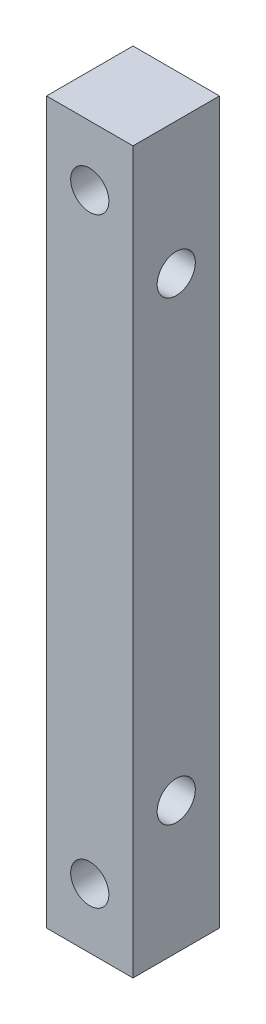
SolidWorks part; units mm, degrees
material "6061-T6 (SS)"
ref_plane "Front Plane" through (0, 0, 0) normal (0, 0, 1) x (1, 0, 0)
ref_plane "Top Plane" through (0, 0, 0) normal (0, 1, 0) x (1, 0, 0)
ref_plane "Right Plane" through (0, 0, 0) normal (1, 0, 0) x (0, 0, -1)
sketch "Sketch1" plane through (0, 0, 0) normal (0, 1, 0) x (1, 0, 0)
  line L1 (-4.572, 4.572) -> (4.572, 4.572)
  line L2 (-4.572, 4.572) -> (-4.572, -4.572)
  line L3 (-4.572, -4.572) -> (4.572, -4.572)
  line L4 (4.572, 4.572) -> (4.572, -4.572)
  line L5 (-4.572, 4.572) -> (4.572, -4.572) construction
  line L6 (-4.572, -4.572) -> (4.572, 4.572) construction
  point P0 (0, 0)
  dimension "D1" = 9.144
extrude "Boss-Extrude1" add sketch "Sketch1" along normal blind 76.2
sketch "Sketch3" plane through (0, 0, 4.572) normal (0, 0, 1) x (1, 0, 0)
  line L0 (0, 69.85) -> (0, 6.35) construction
  line L1 (4.572, 76.2) -> (4.572, 0) construction
  point P3 (0, 38.1)
  point P8 (4.572, 38.1)
  dimension "D1" = 63.5
hole_wizard "Tap Drill for #10-32 Tap1" positions "Sketch4" profile "Sketch6" hole size "#10-32" standard "ANSI Inch" end condition through all
sketch "Sketch4" plane through (0, 0, 4.572) normal (0, 0, 1) x (1, 0, 0)
  point P0 (0, 69.85)
  point P3 (0, 6.35)
sketch "Sketch6" plane through (0, 69.85, 4.572) normal (1, 0, 0) x (0, -1, 0)
  line L0 (0, 0) -> (0, 9.144)
  line L1 (0, 9.144) -> (2.0193, 9.144)
  line L2 (2.0193, 9.144) -> (2.0193, 0)
  line L5 (2.0193, 0) -> (0, 0)
  line L11 (0, -6.35) -> (0, 107.95) construction
  dimension "Thru Hole Dia." = 4.0386
  dimension "Thru Hole Depth" = 9.144
sketch "Sketch7" plane through (4.572, 0, 0) normal (1, 0, 0) x (0, 0, -1)
  line L0 (0, 62.23) -> (0, 13.97) construction
  line L1 (-4.572, 76.2) -> (-4.572, 0) construction
  line L2 (-4.572, 0) -> (4.572, 0) construction
  point P2 (-4.572, 38.1)
  point P3 (0, 38.1)
  point P8 (0, 0)
  dimension "D1" = 48.26
hole_wizard "Tap Drill for #10-32 Tap2" positions "Sketch10" profile "Sketch11" hole size "#10-32" standard "ANSI Inch" end condition through all
sketch "Sketch10" plane through (4.572, 0, 0) normal (1, 0, 0) x (0, 0, -1)
  point P0 (0, 62.23)
  point P3 (0, 13.97)
sketch "Sketch11" plane through (4.572, 62.23, 0) normal (0, 1, 0) x (0, 0, -1)
  line L0 (0, 0) -> (0, 9.144)
  line L1 (0, 9.144) -> (2.0193, 9.144)
  line L2 (2.0193, 9.144) -> (2.0193, 0)
  line L5 (2.0193, 0) -> (0, 0)
  line L11 (0, -6.35) -> (0, 107.95) construction
  dimension "Thru Hole Dia." = 4.0386
  dimension "Thru Hole Depth" = 9.144
